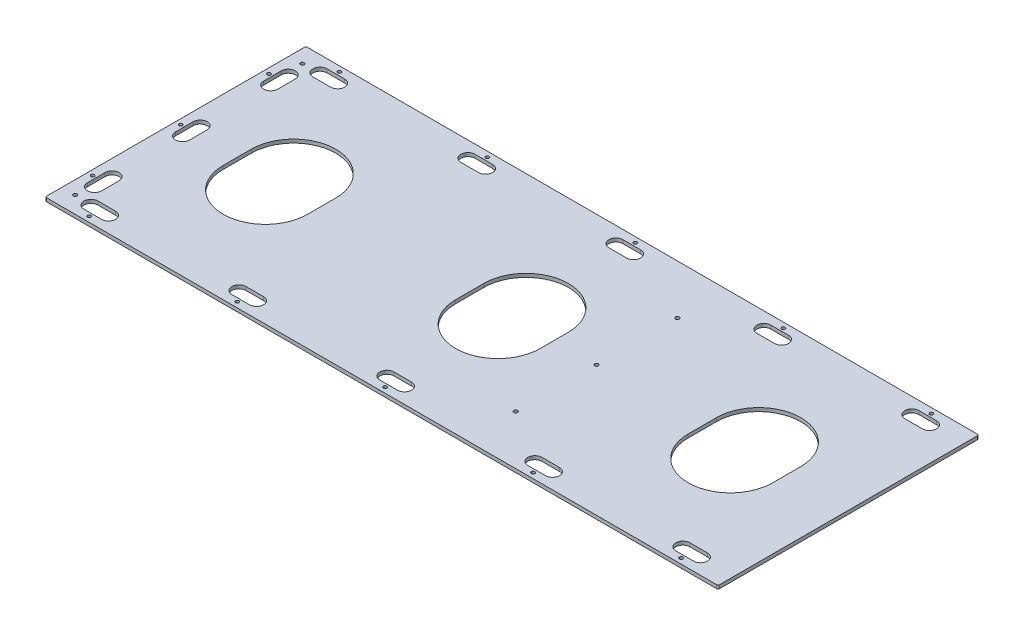
SolidWorks part; units mm, degrees
material "PC High Viscosity"
ref_plane "Front Plane" through (0, 0, 0) normal (0, 0, 1) x (1, 0, 0)
ref_plane "Top Plane" through (0, 0, 0) normal (0, 1, 0) x (1, 0, 0)
ref_plane "Right Plane" through (0, 0, 0) normal (1, 0, 0) x (0, 0, -1)
sketch "Sketch1" plane through (0, 0, 0) normal (0, 1, 0) x (1, 0, 0)
  line L0 (0, 0) -> (0, 469.9)
  line L1 (0, 469.9) -> (1212.85, 469.9)
  line L5 (1212.85, 0) -> (0, 0)
  line L6 (1212.85, 0) -> (1212.85, 469.9)
  dimension "D1" = 469.9
  dimension "D3" = 1212.85
extrude "Boss-Extrude1" add sketch "Sketch1" along normal blind 6.35
sketch "Sketch2" plane through (0, 6.35, 0) normal (0, 1, 0) x (1, 0, 0)
  line L0 (0, 234.95) -> (1212.85, 234.95) construction
  line L1 (0, 469.9) -> (0, 0) construction
  line L2 (1212.85, 0) -> (1212.85, 469.9) construction
  line L3 (187.325, 260.35) -> (187.325, 209.55) construction
  line L4 (263.525, 260.35) -> (263.525, 209.55)
  line L5 (111.125, 260.35) -> (111.125, 209.55)
  line L6 (606.425, 260.35) -> (606.425, 209.55) construction
  line L7 (682.625, 260.35) -> (682.625, 209.55)
  line L8 (530.225, 260.35) -> (530.225, 209.55)
  line L9 (1025.525, 260.35) -> (1025.525, 209.55) construction
  line L10 (1101.725, 260.35) -> (1101.725, 209.55)
  line L11 (949.325, 260.35) -> (949.325, 209.55)
  arc A3 (263.525, 260.35) -> (111.125, 260.35) centre (187.325, 260.35) ccw
  arc A4 (111.125, 209.55) -> (263.525, 209.55) centre (187.325, 209.55) ccw
  arc A5 (682.625, 260.35) -> (530.225, 260.35) centre (606.425, 260.35) ccw
  arc A6 (530.225, 209.55) -> (682.625, 209.55) centre (606.425, 209.55) ccw
  arc A7 (1101.725, 260.35) -> (949.325, 260.35) centre (1025.525, 260.35) ccw
  arc A8 (949.325, 209.55) -> (1101.725, 209.55) centre (1025.525, 209.55) ccw
  point P2 (187.325, 234.95)
  point P14 (606.425, 234.95)
  point P21 (1025.525, 234.95)
  dimension "D4" = 50.8
  dimension "D3" = 76.2
  dimension "D1" = 419.1
  dimension "D2" = 419.1
extrude "Cut-Extrude1" cut sketch "Sketch2" against normal through all
sketch "Sketch4" plane through (0, 6.35, 0) normal (0, 1, 0) x (1, 0, 0)
  line L0 (9.525, 469.9) -> (9.525, 393.7) construction
  line L1 (1212.85, 469.9) -> (0, 469.9) construction
  line L2 (9.525, 393.7) -> (9.525, 234.95) construction
  line L3 (9.525, 234.95) -> (9.525, 76.2) construction
  line L4 (9.525, 76.2) -> (9.525, 0) construction
  line L5 (0, 0) -> (1212.85, 0) construction
  line L6 (0, 469.9) -> (0, 0) construction
  line L7 (0, 460.375) -> (69.85, 460.375) construction
  line L8 (0, 9.525) -> (69.85, 9.525) construction
  line L9 (53.975, 441.325) -> (85.725, 441.325) construction
  line L12 (28.575, 250.825) -> (28.575, 219.075) construction
  line L13 (41.275, 250.825) -> (41.275, 219.075)
  line L14 (15.875, 250.825) -> (15.875, 219.075)
  line L15 (53.975, 454.025) -> (85.725, 454.025)
  line L18 (53.975, 428.625) -> (85.725, 428.625)
  line L19 (53.975, 28.575) -> (85.725, 28.575) construction
  line L20 (53.975, 41.275) -> (85.725, 41.275)
  line L21 (53.975, 15.875) -> (85.725, 15.875)
  line L22 (28.575, 60.325) -> (28.575, 92.075) construction
  line L23 (15.875, 60.325) -> (15.875, 92.075)
  line L24 (41.275, 60.325) -> (41.275, 92.075)
  line L25 (28.575, 377.825) -> (28.575, 409.575) construction
  line L26 (15.875, 377.825) -> (15.875, 409.575)
  line L27 (41.275, 377.825) -> (41.275, 409.575)
  circle A0 centre (9.525, 393.7) radius 3.175
  circle A1 centre (9.525, 234.95) radius 3.175
  circle A2 centre (9.525, 76.2) radius 3.175
  circle A3 centre (69.85, 460.375) radius 3.175
  circle A4 centre (69.85, 9.525) radius 3.175
  arc A7 (41.275, 250.825) -> (15.875, 250.825) centre (28.575, 250.825) ccw
  arc A8 (15.875, 219.075) -> (41.275, 219.075) centre (28.575, 219.075) ccw
  arc A11 (53.975, 454.025) -> (53.975, 428.625) centre (53.975, 441.325) ccw
  arc A12 (85.725, 428.625) -> (85.725, 454.025) centre (85.725, 441.325) ccw
  arc A13 (53.975, 41.275) -> (53.975, 15.875) centre (53.975, 28.575) ccw
  arc A14 (85.725, 15.875) -> (85.725, 41.275) centre (85.725, 28.575) ccw
  arc A15 (15.875, 60.325) -> (41.275, 60.325) centre (28.575, 60.325) ccw
  arc A16 (41.275, 92.075) -> (15.875, 92.075) centre (28.575, 92.075) ccw
  arc A17 (15.875, 377.825) -> (41.275, 377.825) centre (28.575, 377.825) ccw
  arc A18 (41.275, 409.575) -> (15.875, 409.575) centre (28.575, 409.575) ccw
  point P22 (69.85, 441.325)
  point P28 (28.575, 234.95)
  point P35 (69.85, 28.575)
  point P42 (28.575, 76.2)
  point P49 (28.575, 393.7)
  dimension "D3" = 6.35
  dimension "D9" = 12.7
  dimension "D1" = 9.525
  dimension "D2" = 76.2
  dimension "D4" = 69.85
  dimension "D5" = 9.525
  dimension "D6" = 9.525
  dimension "D8" = 19.05
  dimension "D10" = 31.75
  dimension "D11" = 19.05
  dimension "D12" = 19.05
extrude "Cut-Extrude3" cut sketch "Sketch4" against normal through all
pattern_linear "LPattern1" count 5 spacing 266.7 along (1, 0, 0) of face at (69.85, 0, -457.2) of face at (69.85, 0, -6.35) of face at (69.85, 3.175, -41.275) of face at (92.075, 3.175, -28.575) of face at (47.625, 3.175, -28.575) of face at (69.85, 3.175, -15.875) of face at (47.625, 3.175, -441.325) of face at (69.85, 3.175, -454.025) of face at (92.075, 3.175, -441.325) of face at (69.85, 3.175, -428.625)
fillet "Fillet1" radius 2.54 4 edges at (1212.85, 3.175, 0) (1212.85, 3.175, -469.9) (0, 3.175, 0) (0, 3.175, -469.9)
sketch "Sketch5" plane through (0, 6.35, 0) normal (0, 1, 0) x (1, 0, 0)
  line L0 (758.825, 380.746) -> (758.825, 469.9) construction
  line L1 (1210.31, 469.9) -> (2.54, 469.9) construction
  line L2 (758.825, 380.746) -> (758.825, 234.95) construction
  line L3 (758.825, 234.95) -> (758.825, 89.154) construction
  line L4 (758.825, 89.154) -> (758.825, 0) construction
  line L5 (2.54, 0) -> (1210.31, 0) construction
  line L6 (0, 467.36) -> (0, 2.54) construction
  line L7 (1212.85, 2.54) -> (1212.85, 467.36) construction
  circle A0 centre (23.8125, 439.7375) radius 3.3782
  circle A1 centre (23.8125, 30.1625) radius 3.3782
  circle A2 centre (758.825, 89.154) radius 3.3782
  circle A3 centre (758.825, 234.95) radius 3.3782
  circle A4 centre (758.825, 380.746) radius 3.3782
  dimension "D1" = 6.7564
  dimension "D3" = 89.154
  dimension "17.875" = 454.025
  dimension "D4" = 30.1625
  dimension "D6" = 30.1625
  dimension "D7" = 23.8125
extrude "Cut-Extrude4" cut sketch "Sketch5" against normal up to surface (6.35 mm away) up to face at (1136.65, 0, -457.2)
equation "\"D6@Sketch4\"=\"D1@Sketch4\""
equation "\"D5@Sketch4\"=\"D1@Sketch4\""
equation "\"D4@Sketch4\"=2.75"
